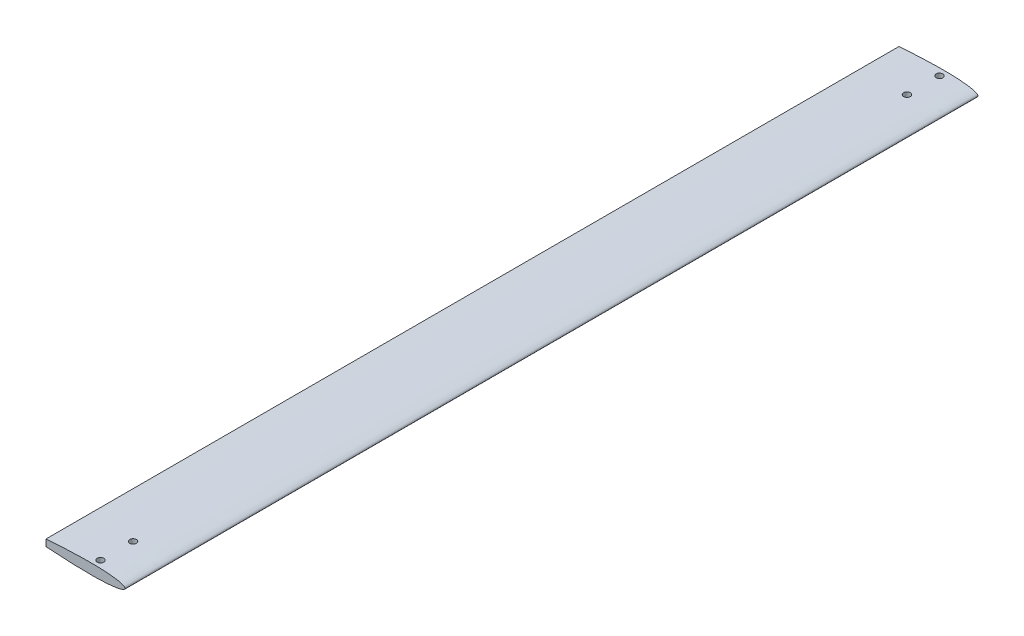
SolidWorks part; units mm, degrees
ref_plane "Front Plane" through (0, 0, 0) normal (0, 0, 1) x (1, 0, 0)
ref_plane "Top Plane" through (0, 0, 0) normal (0, 1, 0) x (1, 0, 0)
ref_plane "Right Plane" through (0, 0, 0) normal (1, 0, 0) x (0, 0, -1)
sketch "Sketch1" plane through (0, 0, 0) normal (0, 0, 1) x (1, 0, 0)
  line L0 (-85.0136, 3.6113) -> (-85.0136, -3.6113)
  spline S0 degree 3 poles (-85.0136, 3.6113) (-83.9513, 3.6872) (-80.7833, 3.9137) (-75.4603, 4.2568) (-69.0215, 4.6375) (-62.5113, 4.9731) (-56.001, 5.2536) (-49.5619, 5.4661) (-43.2645, 5.5994) (-37.1777, 5.6436) (-31.3681, 5.591) (-25.8994, 5.4367) (-20.8312, 5.1793) (-16.2189, 4.821) (-12.1127, 4.3671) (-8.5561, 3.8276) (-5.5878, 3.2107) (-3.2296, 2.5378) (-1.5067, 1.7989) (-0.359, 1.0356) (0.1484, 0) (-0.359, -1.0356) (-1.5067, -1.7989) (-3.2296, -2.5378) (-5.5878, -3.2107) (-8.5561, -3.8276) (-12.1127, -4.3671) (-16.2189, -4.821) (-20.8312, -5.1793) (-25.8994, -5.4367) (-31.3681, -5.591) (-37.1777, -5.6436) (-43.2645, -5.5994) (-49.5619, -5.4661) (-56.001, -5.2536) (-62.5113, -4.9731) (-69.0215, -4.6375) (-75.4603, -4.2568) (-80.7833, -3.9137) (-83.9513, -3.6872) (-85.0136, -3.6113) knots 0 0 0 0 0.018499 0.055171 0.092655 0.130539 0.168407 0.205846 0.242449 0.277819 0.311577 0.343364 0.372846 0.399719 0.423712 0.444594 0.46218 0.476354 0.487106 0.494669 0.5 0.505331 0.512894 0.523646 0.53782 0.555406 0.576288 0.600281 0.627154 0.656636 0.688423 0.722181 0.757551 0.794154 0.831593 0.869461 0.907345 0.944829 0.981501 1 1 1 1
extrude "Boss-Extrude1" add sketch "Sketch1" along normal mid plane 917.4
ref_plane "Plane1" through (0, -10, 0) normal (0, 1, 0) x (1, 0, 0)
sketch "Sketch2" plane through (0, -10, 0) normal (0, 1, 0) x (1, 0, 0)
  circle A0 centre (-33.9, -451.2) radius 3.6
  circle A1 centre (-33.9, -416.2) radius 3.6
  circle A2 centre (-33.9, 416.2) radius 3.6
  circle A3 centre (-33.9, 451.2) radius 3.6
extrude "Cut-Extrude1" cut sketch "Sketch2" along normal blind 20
